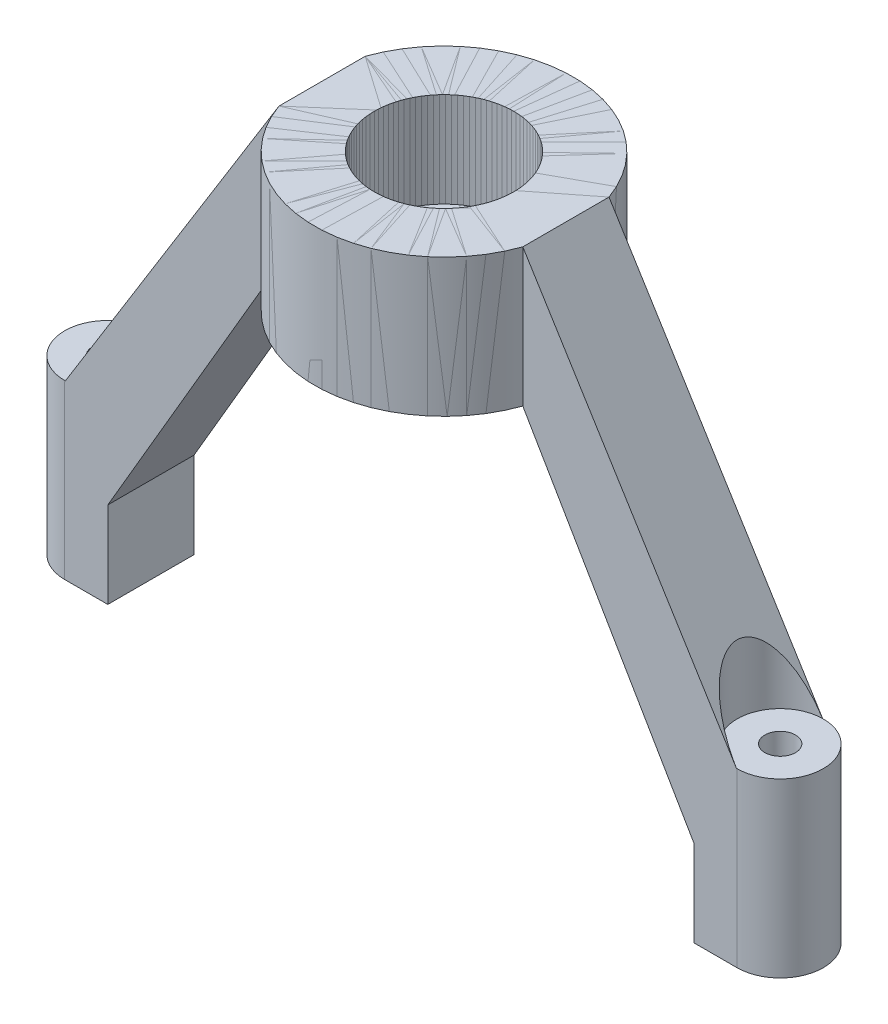
SolidWorks part; units mm, degrees
ref_plane "Front Plane" through (0, 0, 0) normal (0, 0, 1) x (1, 0, 0)
ref_plane "Top Plane" through (0, 0, 0) normal (0, 1, 0) x (1, 0, 0)
ref_plane "Right Plane" through (0, 0, 0) normal (1, 0, 0) x (0, 0, -1)
sketch "Sketch1" plane through (0, 0, 0) normal (0, 1, 0) x (1, 0, 0)
  line L2 (7.0711, 2.5) -> (7.0711, -2.5)
  line L4 (-26.3789, 0) -> (26.3789, 0) construction
  line L5 (-7.0711, 2.5) -> (-18.0711, 2.5) construction
  line L6 (7.0711, -2.5) -> (26.3789, -2.5) construction
  line L7 (0, 0) -> (0, 16.7972) construction
  line L11 (-7.0711, 2.5) -> (-7.0711, -2.5)
  arc A0 (-7.0711, -2.5) -> (7.0711, -2.5) centre (0, 0) ccw
  arc A1 (7.0711, 2.5) -> (-7.0711, 2.5) centre (0, 0) ccw
  circle A2 centre (-19.5, 0) radius 0.889
  circle A3 centre (0, 0) radius 1.875
  circle A8 centre (-19.5, 0) radius 2.5
  dimension "D3" = 15
  dimension "D5" = 3.75
extrude "Boss-Extrude1" add sketch "Sketch1" along normal blind 8 contours L2 A1 L11 A0 A3 region at (6.8649, 0, 0)
extrude "Boss-Extrude2" add sketch "Sketch1<3>" along normal blind 5 from offset 17 separate body contours A8 A2 region at (-21.9293, 0, 0) offset against normal yes
sketch "Sketch1<3>" plane through (0, 0, 0) normal (0, 1, 0) x (1, 0, 0) same geometry as "Sketch1"
sketch "Sketch3" plane through (0, 0, 0) normal (0, 0, 1) x (1, 0, 0)
  line L0 (-7.0711, 8) -> (-19.5, -12.0608)
  line L1 (-19.5, -12.0608) -> (-19.5, -17)
  line L2 (-19.5, -17) -> (-17, -17)
  line L3 (-17, -17) -> (-7.0711, 0)
  line L4 (-7.0711, 0) -> (-7.0711, 8)
sketch "Sketch4" plane through (0, 8, 0) normal (0, 1, 0) x (1, 0, 0)
  circle A0 centre (0, 0) radius 4.05
extrude "Cut-Extrude1" cut sketch "Sketch4" against normal blind 5.5
extrude "Boss-Extrude3" add sketch "Sketch3" along normal blind 2.5 and the other way blind 2.5
sketch "Sketch5" plane through (0, -12, 0) normal (0, 1, 0) x (1, 0, 0)
  line L0 (-19.5, 0.889) -> (-19.5, -0.889) construction
  circle A0 centre (-19.5, 0) radius 2.5
  circle A1 centre (-19.5, 0) radius 0.889
  arc M4 (-19.4624, -0.8882) -> (-19.4624, 0.8882) centre (-19.5, 0) cw
extrude "Cut-Extrude2" cut sketch "Sketch5" along normal through all contours A0
extrude "Cut-Extrude3" cut sketch "Sketch5<3>" against normal through all contours A1 M4 region at (-19.5, -12, 0)
sketch "Sketch5<3>" plane through (0, -12, 0) normal (0, 1, 0) x (1, 0, 0) same geometry as "Sketch5"
sketch "Sketch8" plane through (0, -17, 0) normal (0, -1, 0) x (1, 0, 0)
  line L0 (-19.5, -2.5) -> (-17, -2.5)
  line L1 (-17, -2.5) -> (-17, 2.5)
  line L2 (-17, 2.5) -> (-19.5, 2.5)
  arc A0 (-19.5, 2.5) -> (-19.5, -2.5) centre (-19.5, 0) ccw
  arc A1 (-19.5, 2.5) -> (-19.5, -2.5) centre (-19.5, 0) ccw construction
  circle A2 centre (-19.5, 0) radius 0.889
extrude "Boss-Extrude4" add sketch "Sketch8" along normal blind 5
pattern_circular "CirPattern5" count 2 over 360 about axis through (0, 8, 0) along (0, 1, 0) of bodies 113
